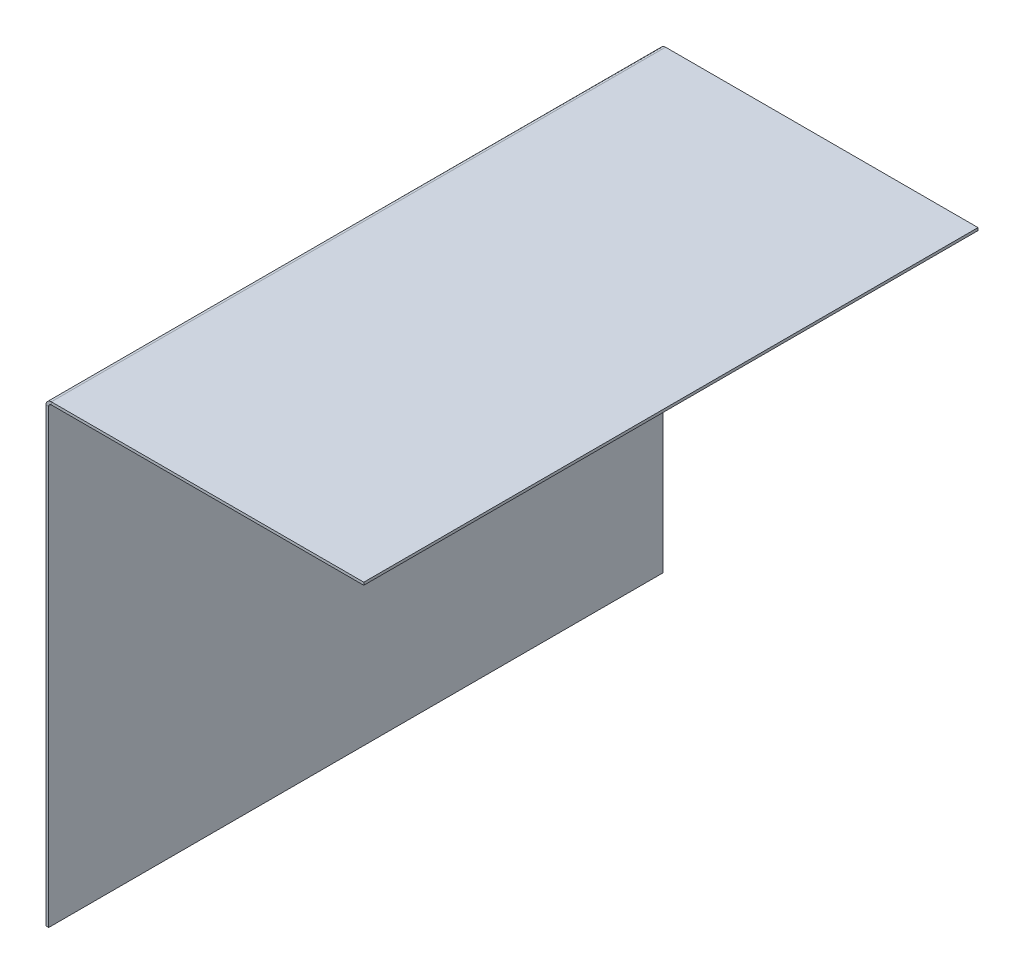
SolidWorks part; units mm, degrees
note: The reader was unsure of these and kept them because the rebuilt part matched: bend radius of "Pliegue base1".
ref_plane "Alzado" through (0, 0, 0) normal (0, 0, 1) x (1, 0, 0)
ref_plane "Planta" through (0, 0, 0) normal (0, 1, 0) x (1, 0, 0)
ref_plane "Vista lateral" through (0, 0, 0) normal (1, 0, 0) x (0, 0, -1)
sketch "Croquis1" plane through (0, 0, 0) normal (0, 0, 1) x (1, 0, 0)
  line L0 (0, 0) -> (118, 0)
  line L1 (0, 0) -> (0, -170)
  dimension "D1" = 118
  dimension "D2" = 170
base flange "Brida base1" sketch "Croquis1" end condition mid plane depth 230 reverse direction no thickness 1 reverse thickness direction no bend radius 1
bend "Pliegue base1" bend radius 1 bend angle 90 parameters "D5"=1
sketch "Croquis6" plane through (0, 0, 115) normal (0, 0, 1) x (1, 0, 0)
  line L4 (118, 1) -> (1, 1)
  line L5 (1, 1) -> (1, 0)
  line L6 (1, 0) -> (118, 0)
  line L7 (118, 0) -> (118, 1)
  line L8 (118, 1) -> (1, 1)
  line L9 (1, 1) -> (1, 0)
  line L10 (1, 0) -> (118, 0)
  line L11 (118, 0) -> (118, 1)
  dimension "D1" = 0
sketch "Líneas de pliegue1" [suppressed] plane through (0, 0, 0) normal (0, 1, 0) x (1, 0, 0)
sketch "Cuadro delimitador1" [suppressed] plane through (0, 0, 0) normal (0, 1, 0) x (1, 0, 0)
sheet metal parameters "Chapa metálica1" thickness 1 parameters "D1"=1
flat pattern "Chapa desplegada1" [suppressed]
sketch "Líneas de pliegue2" plane through (0, 0, 0) normal (1, 0, 0) x (0, 0, -1)
  line L0 (-115, 0.1906) -> (115, 0.1906) construction
  line L1 (-115, 0.1906) -> (115, 0.1906) construction
sketch3d "Cuadro delimitador2" [suppressed]
  line L0 (230, -170, 0) -> (230, 118.3812, 0) construction
  line L1 (0, -170, 0) -> (0, 118.3812, 0) construction
  line L2 (230, -170, 0) -> (0, -170, 0) construction
  line L3 (230, 118.3812, 0) -> (0, 118.3812, 0) construction
bend of the flat pattern "Aplanar-<Pliegue base1>1"
